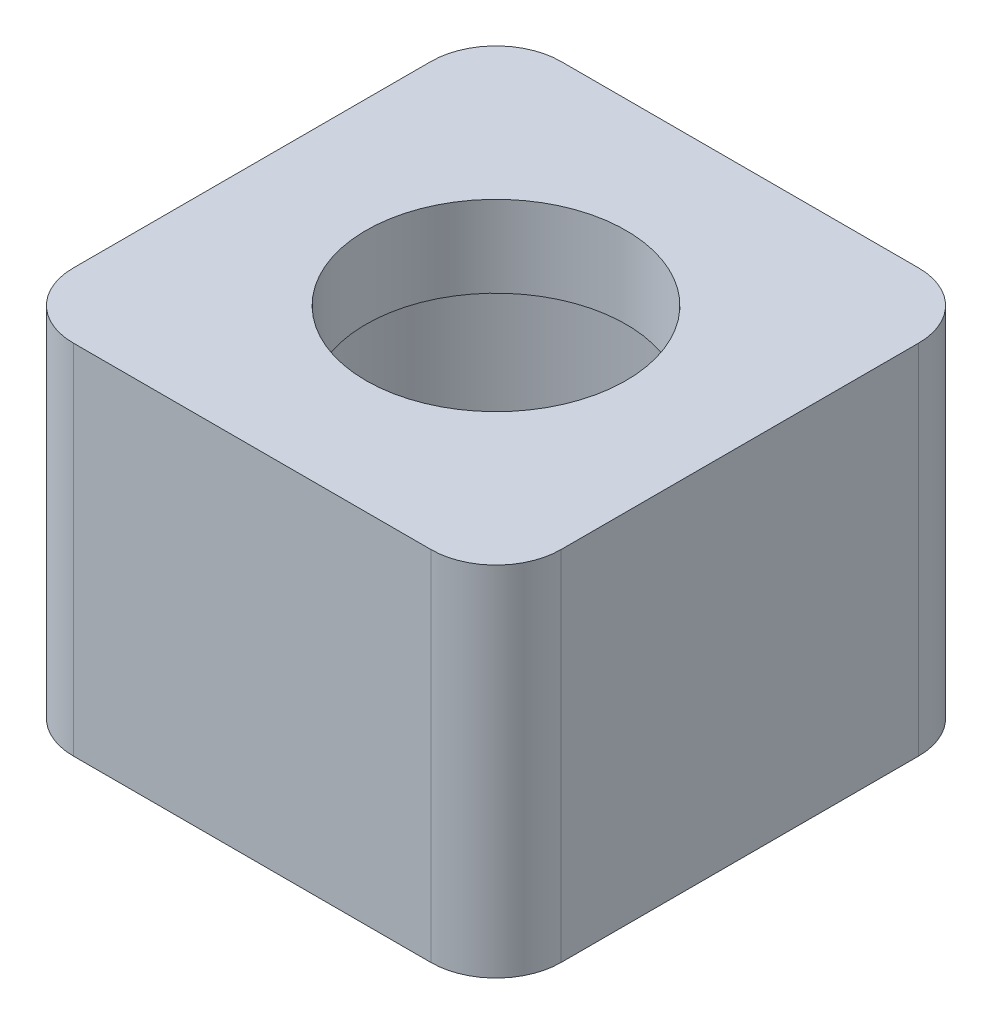
SolidWorks part; units mm, degrees
ref_plane "Front" through (0, 0, 0) normal (0, 0, 1) x (1, 0, 0)
ref_plane "Top" through (0, 0, 0) normal (0, 1, 0) x (1, 0, 0)
ref_plane "Right" through (0, 0, 0) normal (1, 0, 0) x (0, 0, -1)
sketch "Sketch1" plane through (0, 0, 0) normal (0, 1, 0) x (1, 0, 0)
  line L1 (-3.1249, 4.8134) -> (2.3751, 4.8134)
  line L2 (-4.1249, 3.8134) -> (-4.1249, -1.6866)
  line L3 (-3.1249, -2.6866) -> (2.3751, -2.6866)
  line L4 (3.3751, 3.8134) -> (3.3751, -1.6866)
  arc A0 (2.3751, 4.8134) -> (3.3751, 3.8134) centre (2.3751, 3.8134) cw
  arc A1 (2.3751, -2.6866) -> (3.3751, -1.6866) centre (2.3751, -1.6866) ccw
  arc A2 (-4.1249, -1.6866) -> (-3.1249, -2.6866) centre (-3.1249, -1.6866) ccw
  arc A3 (-3.1249, 4.8134) -> (-4.1249, 3.8134) centre (-3.1249, 3.8134) ccw
  point P6 (3.3751, 4.8134)
  point P11 (-4.1249, -2.6866)
  point P14 (-4.1249, 4.8134)
  dimension "D3" = 1
  dimension "D1" = 7.5
  dimension "D2" = 7.5
extrude "Boss-Extrude1" add sketch "Sketch1" along normal blind 5.5
sketch "Sketch2" plane through (0, 5.5, 0) normal (0, 1, 0) x (1, 0, 0)
  line L0 (-0.3749, 4.8134) -> (-0.3749, -2.6866) construction
  line L1 (2.3751, 4.8134) -> (-3.1249, 4.8134) construction
  line L2 (-3.1249, -2.6866) -> (2.3751, -2.6866) construction
  line L3 (-4.1249, 1.0634) -> (3.3751, 1.0634) construction
  line L4 (-4.1249, 3.8134) -> (-4.1249, -1.6866) construction
  line L5 (3.3751, -1.6866) -> (3.3751, 3.8134) construction
  circle A0 centre (-0.3749, 1.0634) radius 2
  dimension "D1" = 4
extrude "Cut-Extrude1" cut sketch "Sketch2" against normal up to surface (5.5 mm away) up to face at (-0.3749, 0, -1.0634)
sketch "Sketch3" plane through (0, 0, 0) normal (0, -1, 0) x (1, 0, 0)
  circle A0 centre (-0.3749, -1.0634) radius 3.25
  dimension "D1" = 6.5
extrude "Cut-Extrude2" cut sketch "Sketch3" against normal blind 4.25
